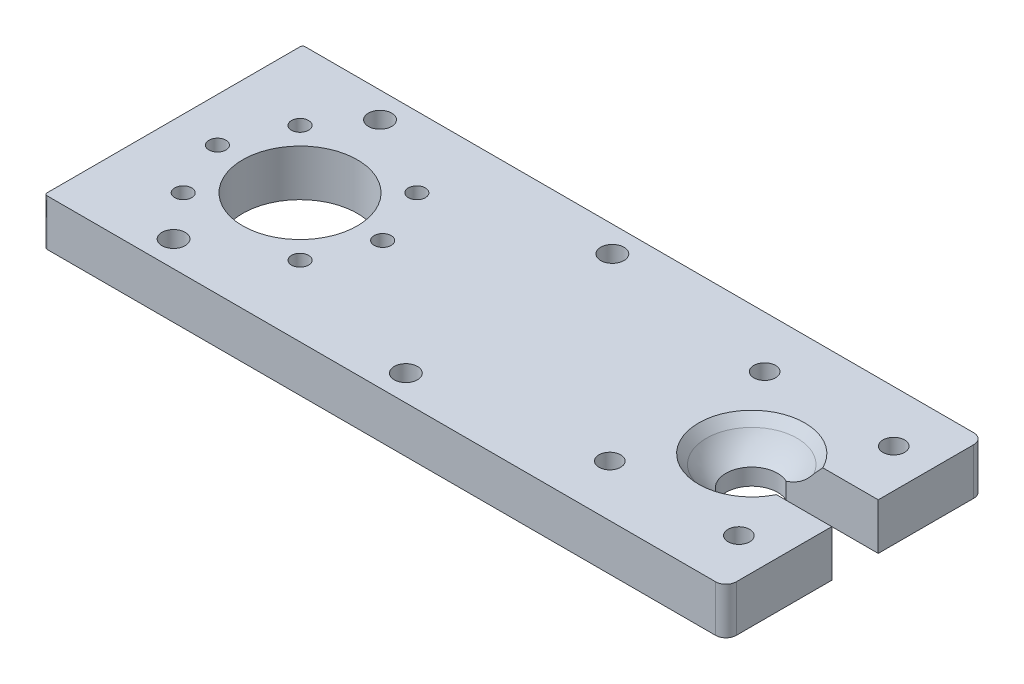
SolidWorks part; units mm, degrees
material "6061-T6 (SS)"
ref_plane "Front Plane" through (0, 0, 0) normal (0, 0, 1) x (1, 0, 0)
ref_plane "Top Plane" through (0, 0, 0) normal (0, 1, 0) x (1, 0, 0)
ref_plane "Right Plane" through (0, 0, 0) normal (1, 0, 0) x (0, 0, -1)
sketch "Sketch1" plane through (0, 0, 0) normal (0, 1, 0) x (1, 0, 0)
  line L1 (-66, -25) -> (66, -25)
  line L2 (-66, -25) -> (-66, 25)
  line L3 (-66, 25) -> (66, 25)
  line L4 (66, -25) -> (66, 25)
  line L5 (-66, -25) -> (66, 25) construction
  line L6 (-66, 25) -> (66, -25) construction
  point P0 (0, 0)
  dimension "D1" = 50
  dimension "D2" = 132
extrude "Boss-Extrude1" add sketch "Sketch1" along normal blind 9
hole_wizard "M4 Tapped Hole1" positions "Sketch2" profile "Sketch4" tap size "M4" standard "ISO"
sketch "Sketch2" plane through (-66, 0, 0) normal (-1, 0, 0) x (0, 0, 1)
  line L2 (-20, 9) -> (-20, 0) construction
  line L3 (-25, 9) -> (25, 9) construction
  line L4 (-25, 0) -> (25, 0) construction
  line L6 (20, 9) -> (20, 0) construction
  line L8 (-25, 9) -> (-25, 0) construction
  line L9 (25, 9) -> (25, 0) construction
  point P0 (-20, 4.5)
  point P2 (20, 4.5)
  dimension "D1" = 5
  dimension "D2" = 5
sketch "Sketch4" plane through (-66, 4.5, -20) normal (0, 1, 0) x (0, 0, 1)
  line L0 (0, 0) -> (0, 15)
  line L1 (0, 15) -> (1.65, 14.0086)
  line L2 (1.65, 14.0086) -> (1.65, 0)
  line L5 (1.65, 0) -> (0, 0)
  line L10 (0, 15) -> (-1.65, 14.0086) construction
  line L11 (0, -6.35) -> (0, 107.95) construction
  dimension "Tap Drill Dia." = 3.3
  dimension "Tap Drill Depth" = 15
  dimension "Drill Angle" = 118
cosmetic thread "Hole Thread1" parameters "D1"=13, "D2"=4
cosmetic thread "Hole Thread2" parameters "D1"=13, "D2"=4
fillet "Fillet1" radius 0.5 2 edges at (-66, 4.5, -25) (-66, 4.5, 25)
sketch "Sketch5" plane through (0, 9, 0) normal (0, 1, 0) x (1, 0, 0)
  line L0 (-66, 24.5) -> (-66, -24.5) construction
  circle A0 centre (-41.5, 0) radius 11.1
  dimension "D1" = 22.2
  dimension "D2" = 24.5
extrude "Cut-Extrude1" cut sketch "Sketch5" against normal through all
ref_plane "Plane1" through (46, 0, 0) normal (-1, 0, 0) x (0, 0, 1)
sketch "Sketch8" plane through (0, 9, 0) normal (0, 1, 0) x (1, 0, 0)
  line L0 (66, 25) -> (-65.5, 25) construction
  line L1 (33.5, -15) -> (58.5, -15) construction
  line L2 (33.5, -15) -> (33.5, 15) construction
  line L3 (33.5, 15) -> (58.5, 15) construction
  line L4 (58.5, -15) -> (58.5, 15) construction
  line L6 (58.5, -15) -> (33.5, 15) construction
  line L7 (58.5, 15) -> (33.5, -15) construction
  line L8 (66, -25) -> (66, 25) construction
  point P4 (33.5, 0)
  point P8 (46, 0)
  dimension "D1" = 10
  dimension "D2" = 20
  dimension "D3" = 25
hole_wizard "M5 Tapped Hole1" positions "Sketch9" profile "Sketch10" tap size "M5" standard "ISO" end condition through all
sketch "Sketch9" plane through (0, 9, 0) normal (0, 1, 0) x (1, 0, 0)
  point P0 (33.5, 15)
  point P3 (33.5, -15)
  point P6 (58.5, -15)
  point P9 (58.5, 15)
sketch "Sketch10" plane through (33.5, 9, -15) normal (1, 0, 0) x (0, 0, 1)
  line L0 (0, 0) -> (0, 9)
  line L1 (0, 9) -> (2.1, 9)
  line L2 (2.1, 9) -> (2.1, 0)
  line L5 (2.1, 0) -> (0, 0)
  line L11 (0, -6.35) -> (0, 107.95) construction
  dimension "Thru Tap Drill Dia." = 4.2
  dimension "Thru Tap Drill Depth" = 9
cosmetic thread "Hole Thread3" parameters "D2"=5
cosmetic thread "Hole Thread4" parameters "D2"=5
cosmetic thread "Hole Thread5" parameters "D2"=5
cosmetic thread "Hole Thread6" parameters "D2"=5
sketch "Sketch11" plane through (0, 0, 0) normal (0, -1, 0) x (1, 0, 0)
  line L0 (-66, -24.5) -> (-66, 24.5) construction
  line L1 (-1, -20) -> (-46, -20)
  line L2 (-1, -20) -> (-1, 20)
  line L3 (-1, 20) -> (-46, 20)
  line L4 (-46, -20) -> (-46, 20)
  line L5 (66, -25) -> (-65.5, -25) construction
  point P4 (-1, 0)
  dimension "D1" = 45
  dimension "D2" = 20
  dimension "D3" = 5
hole_wizard "CSK for M4 Hex Socket Countersunk Cap Screw1" positions "Sketch12" profile "Sketch13" countersink size "M4" standard "ISO" end condition through all
sketch "Sketch12" plane through (0, 0, 0) normal (0, -1, 0) x (-1, 0, 0)
  point P0 (1, -20)
  point P3 (46, -20)
  point P6 (46, 20)
  point P9 (1, 20)
sketch "Sketch13" plane through (-1, 0, 20) normal (1, 0, 0) x (0, 0, -1)
  line L0 (0, 0) -> (0, 9)
  line L1 (0, 9) -> (2.25, 9)
  line L2 (2.25, 9) -> (2.25, 2.23)
  line L3 (2.25, 2.23) -> (4.48, 0)
  line L5 (4.48, 0) -> (0, 0)
  line L6 (-2.25, 2.23) -> (-4.48, 0) construction
  line L11 (0, -6.35) -> (0, 107.95) construction
  dimension "Thru Hole Dia." = 4.5
  dimension "Thru Hole Depth" = 9
  dimension "Near C'Sink Dia." = 8.96
  dimension "Near C'Sink Angle" = 90
sketch "Sketch14" plane through (0, 9, 0) normal (0, 1, 0) x (1, 0, 0)
  circle A1 centre (-41.5, 0) radius 11.1 construction
  circle A2 centre (-41.5, 0) radius 16 construction
  circle A3 centre (-41.5, 0) radius 11.1 construction
  point P4 (-57.5, 0)
  dimension "D1" = 32
hole_wizard "M4 Tapped Hole2" positions "Sketch15" profile "Sketch16" tap size "M4" standard "ISO" end condition through all
sketch "Sketch15" plane through (0, 9, 0) normal (0, 1, 0) x (1, 0, 0)
  point P0 (-57.5, 0)
sketch "Sketch16" plane through (-57.5, 9, 0) normal (1, 0, 0) x (0, 0, 1)
  line L0 (0, 0) -> (0, 9)
  line L1 (0, 9) -> (1.65, 9)
  line L2 (1.65, 9) -> (1.65, 0)
  line L5 (1.65, 0) -> (0, 0)
  line L11 (0, -6.35) -> (0, 107.95) construction
  dimension "Thru Tap Drill Dia." = 3.3
  dimension "Thru Tap Drill Depth" = 9
cosmetic thread "Hole Thread7" parameters "D2"=4
pattern_circular "CirPattern1" count 8 over 360 about axis through (-41.5, 0, 0) along (0, 1, 0) skipping 2, 6 of "M4 Tapped Hole2" reverse direction yes
sketch "Sketch17" plane through (0, 9, 0) normal (0, 1, 0) x (1, 0, 0)
  line L0 (66, 4.5) -> (48.1794, 4.5)
  line L2 (48.1794, -4.5) -> (66, -4.5)
  line L4 (66, 25) -> (-65.5, 25)
  line L5 (-66, 24.5) -> (-66, -24.5)
  line L6 (-65.5, -25) -> (66, -25)
  line L7 (66, -25) -> (66, 25)
  line L8 (66, 25) -> (-65.5, 25)
  line L9 (-66, 24.5) -> (-66, -24.5)
  line L10 (-65.5, -25) -> (66, -25)
  line L11 (66, -25) -> (66, 25)
  arc A0 (48.1794, 4.5) -> (48.1794, -4.5) centre (46, 0) ccw
  arc A2 (-65.5, 25) -> (-66, 24.5) centre (-65.5, 24.5) ccw
  arc A3 (-66, -24.5) -> (-65.5, -25) centre (-65.5, -24.5) ccw
  arc A4 (-65.5, 25) -> (-66, 24.5) centre (-65.5, 24.5) ccw
  arc A5 (-66, -24.5) -> (-65.5, -25) centre (-65.5, -24.5) ccw
  line M26 (66, -25) -> (66, 25)
  dimension "D5" = 10
  dimension "D2" = 20.5
  dimension "D3" = 20.5
  dimension "D4" = 20
  dimension "D1" = 0
extrude "Cut-Extrude2" cut sketch "Sketch17" against normal blind 10 contours L0 A0 L2 M26 region at (53.7824, 9, 0)
sketch "Sketch18" plane through (0, 0, 0) normal (0, 0, 1) x (1, 0, 0)
  line L0 (66, 0) -> (48.1794, 0) construction
  line L1 (48.1794, 9) -> (66, 9) construction
  line L2 (66, 9) -> (66, 0) construction
  line L3 (41, 0) -> (48.1794, 0) construction
  line L4 (48.1794, 9) -> (41, 9) construction
  line L5 (48.1794, 0) -> (66, 0) construction
  line L6 (66, 0) -> (66, 9) construction
  line L7 (66, 9) -> (48.1794, 9) construction
  line L8 (66, 0) -> (48.1794, 0) construction
  line L9 (48.1794, 9) -> (66, 9) construction
  line L10 (66, 9) -> (66, 0) construction
  line L11 (41, 0) -> (48.1794, 0) construction
  line L12 (48.1794, 9) -> (41, 9) construction
  line L13 (48.1794, 0) -> (66, 0) construction
  line L14 (66, 0) -> (66, 9) construction
  line L15 (66, 9) -> (48.1794, 9) construction
  line L16 (41, 9) -> (46, 9) construction
  line L17 (46, 9) -> (46, 14.78) construction
  line L18 (46, 14.78) -> (42.91, 14.78) construction
  line L19 (46, 9) -> (46, 1.0023)
  line L22 (46, 9) -> (55.7928, 9)
  arc A0 (46, 1.0023) -> (55.7928, 9) centre (42.91, 14.78) ccw
  dimension "D4" = 28.24
  dimension "D1" = 5
  dimension "D2" = 5.78
  dimension "D3" = 3.09
revolve "Cut-Revolve1" cut sketch "Sketch18" angle 360 about L19
chamfer "Chamfer1" distance 0.5 distance2 1.5 1 edges at (36.2072, 9, 0) first distance on face at (9.1698, 9, 0)
fillet "Fillet2" radius 2 2 edges at (66, 4.5, -25) (66, 4.5, 25)
